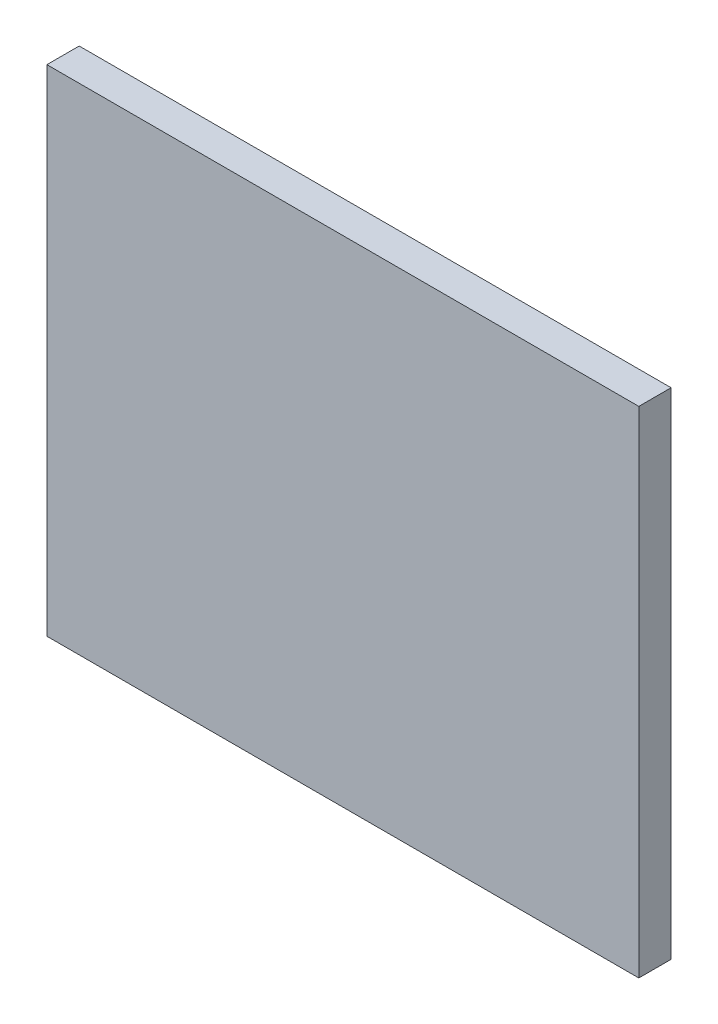
SolidWorks part; units mm, degrees
ref_plane "Front" through (0, 0, 0) normal (0, 0, 1) x (1, 0, 0)
ref_plane "Top" through (0, 0, 0) normal (0, 1, 0) x (1, 0, 0)
ref_plane "Right" through (0, 0, 0) normal (1, 0, 0) x (0, 0, -1)
sketch "Эскиз1" plane through (0, 0, 0) normal (0, 0, 1) x (1, 0, 0)
  line L1 (27.5, 43) -> (-27.5, 43)
  line L2 (27.5, 43) -> (27.5, -3)
  line L3 (27.5, -3) -> (-27.5, -3)
  line L4 (-27.5, 43) -> (-27.5, -3)
extrude "Бобышка-Вытянуть1" add sketch "Эскиз1" along normal blind 3
sketch "Эскиз2" plane through (0, 0, 0) normal (0, 0, -1) x (-1, 0, 0)
  line L0 (-27.5, 20) -> (27.5, 20) construction
  line L1 (-27.5, -3) -> (-27.5, 43) construction
  line L2 (27.5, 43) -> (27.5, -3) construction
  line L3 (0, 20) -> (0, 24.3841) construction
  line L4 (-21.1, 17.5) -> (-24.1, 17.5)
  line L5 (-21.1, 17.5) -> (-21.1, 22.5)
  line L6 (-21.1, 22.5) -> (-24.1, 22.5)
  line L7 (-24.1, 17.5) -> (-24.1, 22.5)
  line L8 (-21.1, 17.5) -> (-24.1, 22.5) construction
  line L9 (-21.1, 22.5) -> (-24.1, 17.5) construction
  line L10 (21.1, 22.5) -> (24.1, 17.5) construction
  line L11 (21.1, 17.5) -> (24.1, 22.5) construction
  line L12 (24.1, 17.5) -> (24.1, 22.5)
  line L13 (21.1, 22.5) -> (24.1, 22.5)
  line L14 (21.1, 17.5) -> (21.1, 22.5)
  line L15 (21.1, 17.5) -> (24.1, 17.5)
  point P6 (-22.6, 20)
  point P18 (22.6, 20)
  dimension "D1" = 3
  dimension "D2" = 5
  dimension "D3" = 3.4
extrude "Бобышка-Вытянуть2" add sketch "Эскиз2" along normal blind 2
chamfer "Фаска1" distance 2 angle 45 6 edges at (-22.6, 17.5, 0) (-21.1, 20, 0) (-22.6, 22.5, 0) (22.6, 22.5, 0) (21.1, 20, 0) (22.6, 17.5, 0)
